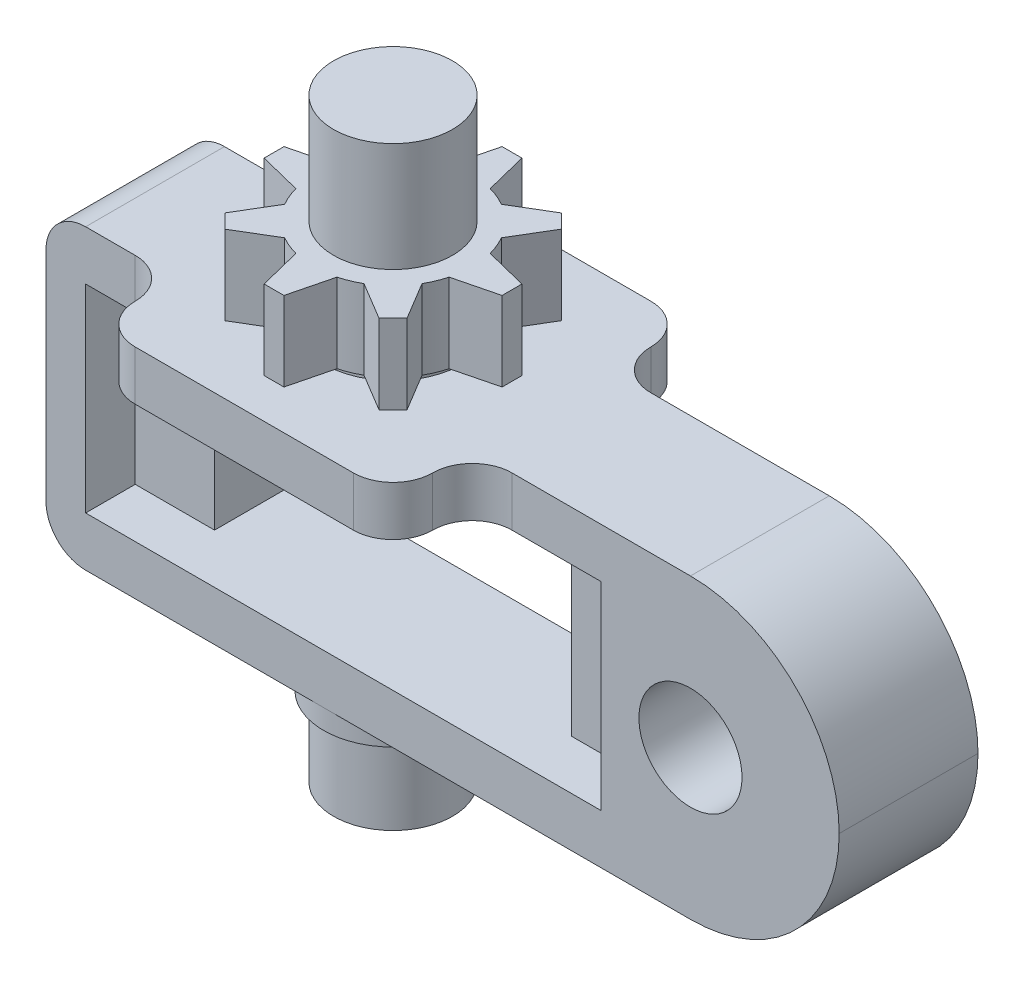
SolidWorks part; units mm, degrees
ref_plane "Front Plane" through (0, 0, 0) normal (0, 0, 1) x (1, 0, 0)
ref_plane "Top Plane" through (0, 0, 0) normal (0, 1, 0) x (1, 0, 0)
ref_plane "Right Plane" through (0, 0, 0) normal (1, 0, 0) x (0, 0, -1)
sketch "Sketch2" plane through (0, 0, 0) normal (0, 0, 1) x (1, 0, 0)
  line L1 (-25.4, -9.525) -> (25.4, -9.525)
  line L2 (-25.4, -9.525) -> (-25.4, 9.525)
  line L3 (-25.4, 9.525) -> (25.4, 9.525)
  line L4 (25.4, -9.525) -> (25.4, 9.525)
  line L5 (-25.4, -9.525) -> (25.4, 9.525) construction
  line L6 (-25.4, 9.525) -> (25.4, -9.525) construction
  point P0 (0, 0)
  dimension "D1" = 19.05
  dimension "D2" = 50.8
extrude "Boss-Extrude1" add sketch "Sketch2" along normal mid plane 8.89
sketch "Sketch4" plane through (2.107, 4.8704, 4.445) normal (0, 0, 1) x (1, 0, 0)
  line L0 (-8.457, -4.8704) -> (-2.107, -4.8704) construction
  line L1 (-24.967, -11.2204) -> (8.053, -11.2204)
  line L2 (-24.967, -11.2204) -> (-24.967, 1.4796)
  line L3 (-24.967, 1.4796) -> (8.053, 1.4796)
  line L4 (8.053, -11.2204) -> (8.053, 1.4796)
  line L5 (-24.967, -11.2204) -> (8.053, 1.4796) construction
  line L6 (-24.967, 1.4796) -> (8.053, -11.2204) construction
  point P0 (-8.457, -4.8704)
  point P8 (-7.6915, 0)
  point P9 (-2.107, -4.8704)
  point P11 (-21.1229, 1.4796)
  point P12 (-22.9537, 1.4796)
  point P13 (-25.46, 1.4796)
  dimension "D1" = 12.7
  dimension "D2" = 33.02
  dimension "D3" = 6.35
extrude "Cut-Extrude1" cut sketch "Sketch4" against normal blind 3.175 and the other way through all
sketch "Sketch6" plane through (0, 0, -4.445) normal (0, 0, -1) x (-1, 0, 0)
  line L1 (-5.08, -6.35) -> (17.78, -6.35)
  line L2 (-5.08, -6.35) -> (-5.08, 6.35)
  line L3 (-5.08, 6.35) -> (17.78, 6.35)
  line L4 (-10.16, 6.35) -> (-10.16, -6.35)
  line L5 (22.86, 6.35) -> (-10.16, 6.35)
  line L6 (22.86, -6.35) -> (22.86, 6.35)
  line L7 (-10.16, -6.35) -> (22.86, -6.35)
  line L8 (-10.16, 6.35) -> (-10.16, -6.35) construction
  line L9 (22.86, 6.35) -> (-10.16, 6.35) construction
  line L10 (22.86, -6.35) -> (22.86, 6.35) construction
  line L11 (-10.16, -6.35) -> (22.86, -6.35) construction
  line L12 (17.78, -6.35) -> (17.78, 6.35)
  line L13 (-5.08, -6.35) -> (17.78, 6.35) construction
  line L14 (-5.08, 6.35) -> (17.78, -6.35) construction
  point P2 (6.35, 0)
  dimension "D2" = 5.08
  dimension "D3" = 22.86
  dimension "D1" = 0
extrude "Cut-Extrude2" cut sketch "Sketch6" against normal through all
fillet "Fillet2" radius 9.525 2 edges at (25.4, -9.525, 0) (25.4, 9.525, 0)
sketch "Sketch9" plane through (0, 0, 4.445) normal (0, 0, 1) x (1, 0, 0)
  circle A0 centre (15.875, 0) radius 3.302
  dimension "D1" = 6.604
extrude "Cut-Extrude4" cut sketch "Sketch9" against normal through all
sketch "Sketch10" plane through (0, 9.525, 0) normal (0, 1, 0) x (1, 0, 0)
  line L0 (0, 0) -> (-7.62, 0) construction
  line L2 (-17.145, -9.525) -> (1.905, -9.525)
  line L3 (-17.145, -9.525) -> (-17.145, 9.525)
  line L4 (-17.145, 9.525) -> (1.905, 9.525)
  line L5 (1.905, -9.525) -> (1.905, 9.525)
  line L6 (-17.145, -9.525) -> (1.905, 9.525) construction
  line L7 (-17.145, 9.525) -> (1.905, -9.525) construction
  point P7 (-10.4368, 0)
  dimension "D1" = 19.05
  dimension "D2" = 19.05
  dimension "D3" = 7.62
extrude "Boss-Extrude2" add sketch "Sketch10" against normal up to surface (3.175 mm away) up to face at (-6.35, 6.35, 0.635)
fillet "Fillet1" radius 2.54 10 edges at (-25.4, -9.525, 0) (-25.4, 9.525, 0) (-17.145, 7.9375, -4.445) (-17.145, 7.9375, -9.525) (1.905, 7.9375, -9.525) (1.905, 7.9375, -4.445) (1.905, 7.9375, 4.445) (-17.145, 7.9375, 4.445) (-17.145, 7.9375, 9.525) (1.905, 7.9375, 9.525)
sketch "Sketch11" plane through (0, 9.525, 0) normal (0, 1, 0) x (1, 0, 0)
  line L1 (-14.605, -9.525) -> (-0.635, -9.525) construction
  line L2 (-14.605, -9.525) -> (-14.605, 9.525) construction
  line L3 (-14.605, 9.525) -> (-0.635, 9.525) construction
  line L4 (-0.635, -9.525) -> (-0.635, 9.525) construction
  line L5 (-14.605, -9.525) -> (-0.635, 9.525) construction
  line L6 (-14.605, 9.525) -> (-0.635, -9.525) construction
  circle A0 centre (-7.62, 0) radius 3.81
  point P0 (-7.62, 0)
  dimension "D1" = 7.62
extrude "Boss-Extrude3" add sketch "Sketch11" along normal blind 12.7
sketch "Sketch12" plane through (0, -9.525, 0) normal (0, -1, 0) x (1, 0, 0)
  circle A0 centre (-7.62, 0) radius 3.81 construction
  circle A1 centre (-7.62, 0) radius 3.81
extrude "Boss-Extrude4" add sketch "Sketch12" along normal blind 6.35
sketch "Sketch13" plane through (0, 9.525, 0) normal (0, 1, 0) x (1, 0, 0)
  circle A0 centre (-7.62, 0) radius 4.445
  circle A1 centre (-7.62, 0) radius 3.81 construction
  point P2 (-9.4385, 0)
  dimension "D1" = 8.89
extrude "Boss-Extrude5" add sketch "Sketch13" along normal blind 0.635
sketch "Sketch14" plane through (0, 10.16, 0) normal (0, 1, 0) x (1, 0, 0)
  circle A0 centre (-7.62, 0) radius 5.08
  dimension "D1" = 10.16
extrude "Boss-Extrude6" add sketch "Sketch14" along normal blind 5.08
sketch "Sketch15" plane through (0, 15.24, 0) normal (0, 1, 0) x (1, 0, 0)
  line L0 (-7.62, 0) -> (-7.62, 5.08) construction
  line L1 (-7.62, 5.08) -> (-7.62, 7.62) construction
  line L2 (-8.255, 7.62) -> (-6.985, 7.62)
  line L3 (-8.255, 7.62) -> (-8.9348, 4.9069)
  line L4 (-8.9348, 4.9069) -> (-6.3052, 4.9069)
  line L5 (-6.985, 7.62) -> (-6.3052, 4.9069)
  line L6 (-8.9348, 4.9069) -> (-7.62, 0) construction
  line L7 (-6.3052, 4.9069) -> (-7.62, 0) construction
  circle A0 centre (-7.62, 0) radius 5.08 construction
  point P9 (-7.62, 7.62)
  dimension "D1" = 1.27
  dimension "D2" = 2.54
  dimension "D3" = 30
extrude "Boss-Extrude7" add sketch "Sketch15" against normal up to surface (5.08 mm away) up to face at (-7.62, 10.16, 4.445)
pattern_circular "CirPattern1" count 8 over 360 about axis through (-7.62, 15.24, 0) along (0, -1, 0) of "Boss-Extrude7" reverse direction yes
sketch "Sketch16" plane through (0, -9.525, 0) normal (0, -1, 0) x (1, 0, 0)
  circle A0 centre (-7.62, 0) radius 4.445
  dimension "D1" = 8.89
extrude "Boss-Extrude8" add sketch "Sketch16" along normal blind 1.27
